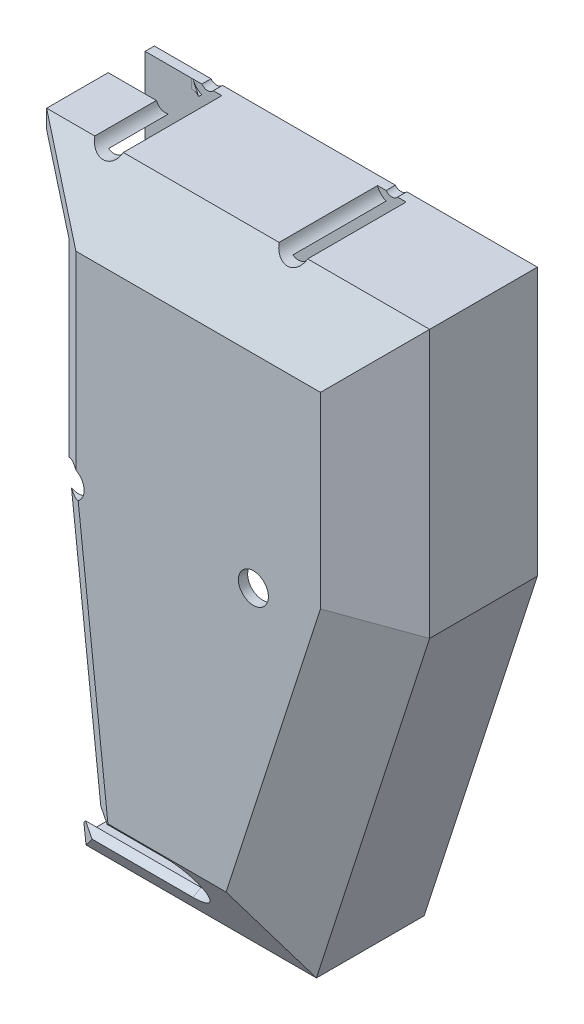
SolidWorks part; units mm, degrees
material "ABS"
ref_plane "Front Plane" through (0, 0, 0) normal (0, 0, 1) x (1, 0, 0)
ref_plane "Top Plane" through (0, 0, 0) normal (0, 1, 0) x (1, 0, 0)
ref_plane "Right Plane" through (0, 0, 0) normal (1, 0, 0) x (0, 0, -1)
sketch "Sketch1" plane through (0, 0, 0) normal (0, 0, 1) x (1, 0, 0)
  line L0 (-33.5, -29) -> (-33.5, -5) construction
  line L1 (-24.9678, -105) -> (-33.5, -29) construction
  line L2 (-24.9678, -105) -> (24.9678, -105) construction
  line L3 (49.5, -29) -> (24.9678, -105) construction
  line L4 (49.5, 29) -> (49.5, -29) construction
  line L5 (-33.5, -29) -> (-33.5, 29)
  line L6 (-24.9678, -105) -> (-33.5, -29)
  line L7 (-24.9678, -105) -> (24.9678, -105)
  line L8 (49.5, -29) -> (24.9678, -105)
  line L9 (49.5, 29) -> (49.5, -29)
  line L10 (49.5, 29) -> (-33.5, 29)
extrude "Extrude1" add sketch "Sketch1" along normal blind 32
chamfer "Chamfer1" distance 15 angle 30 6 edges at (-33.5, 0, 32) (-29.2339, -67, 32) (37.2339, -67, 32) (49.5, 0, 32) (8, 29, 32) (0, -105, 32) first distance on face at (5.3333, -35, 32)
sketch "Sketch2" plane through (-33.5, 0, 0) normal (-1, 0, 0) x (0, 0, 1)
  line L0 (2, 27) -> (22.185, 27)
  line L1 (22.185, 27) -> (30, 13.4641)
  line L2 (30, 13.4641) -> (30, -89.4641)
  line L3 (30, -89.4641) -> (22.185, -103)
  line L4 (22.185, -103) -> (2, -103)
  line L5 (2, -103) -> (2, 27)
  line L6 (0, 29) -> (0, -29) construction
  line L7 (23.3397, 29) -> (0, 29) construction
  line L8 (32, 14) -> (23.3397, 29) construction
  line L9 (32, -90) -> (23.3397, -105) construction
  line L10 (32, 14) -> (32, -28.1606) construction
  line L11 (23.3397, -105) -> (0, -105) construction
  dimension "D1" = 2
  dimension "D2" = 2
  dimension "D3" = 2
  dimension "D4" = 2
  dimension "D5" = 2
  dimension "D6" = 2
extrude "Cut-Extrude2" cut sketch "Sketch2" against normal blind 20
shell "Shell1" thickness 2 removed face at (-13.5, -38, 18.0617)
sketch "Sketch3" plane through (0, 0, 2) normal (0, 0, 1) x (1, 0, 0)
  line L0 (39.5, 0) -> (0, 0) construction
  line L1 (39.5, -5) -> (0, -5)
  line L2 (39.5, 5) -> (0, 5)
  circle A0 centre (19.9678, 30) radius 1.6 construction
  circle A1 centre (-19.9678, 30) radius 1.6 construction
  circle A2 centre (19.9678, -30) radius 1.6 construction
  circle A3 centre (-19.9678, -30) radius 1.6 construction
  circle A4 centre (19.9678, 30) radius 1.6
  circle A5 centre (-19.9678, 30) radius 1.6
  circle A6 centre (19.9678, -30) radius 1.6
  circle A7 centre (-19.9678, -30) radius 1.6
  circle A8 centre (0, -54.5) radius 20
  arc A9 (39.5, -5) -> (39.5, 5) centre (39.5, 0) ccw
  arc A10 (0, 5) -> (0, -5) centre (0, 0) ccw
  point P19 (19.75, 0)
  dimension "D1" = 40
  dimension "D2" = 5
extrude "Cut-Extrude3" cut sketch "Sketch3" against normal blind 20
sketch "Sketch4" plane through (0, 0, 2) normal (0, 0, 1) x (1, 0, 0)
  circle A0 centre (-19.9678, -30) radius 3.25
  circle A1 centre (-19.9678, 30) radius 3.25
  circle A2 centre (19.9678, 30) radius 3.25
  circle A3 centre (19.9678, -30) radius 3.25
  dimension "D1" = 6.5
extrude "Cut-Extrude5" cut sketch "Sketch4" along normal blind 39
sketch "Sketch6" plane through (0, 29, 0) normal (0, 1, 0) x (1, 0, 0)
  line L0 (-43.2864, -6) -> (-23.5, -6) construction
  line L1 (-43.2864, -2) -> (-23.5, -2)
  line L2 (-43.2864, -10) -> (-23.5, -10)
  line L3 (-21.2178, -2) -> (-33.5, -2) construction
  line L4 (-33.5, -23.3397) -> (-33.5, 0) construction
  arc A0 (-43.2864, -2) -> (-43.2864, -10) centre (-43.2864, -6) ccw
  arc A1 (-23.5, -10) -> (-23.5, -2) centre (-23.5, -6) ccw
  point P2 (-33.3932, -6)
  dimension "D1" = 4
  dimension "D2" = 10
extrude "Cut-Extrude6" cut sketch "Sketch6" against normal blind 9
sketch "Sketch7" plane through (0, 0, 2) normal (0, 0, 1) x (1, 0, 0)
  line L0 (20.0322, -100) -> (-19.9678, -100) construction
  line L1 (20.0322, -104) -> (-19.9678, -104)
  line L2 (20.0322, -96) -> (-19.9678, -96)
  arc A0 (20.0322, -104) -> (20.0322, -96) centre (20.0322, -100) ccw
  arc A1 (-19.9678, -96) -> (-19.9678, -104) centre (-19.9678, -100) ccw
  point P4 (0.0322, -100)
  dimension "D1" = 4
extrude "Cut-Extrude7" cut sketch "Sketch7" along normal blind 9 and the other way blind 9
sketch "Sketch8" plane through (0, -35.3564, 61.2391) normal (0, 0.5, -0.866) x (-1, 0, 0)
  line L0 (24.3945, -68.4782) -> (-0.6055, -68.4782) construction
  line L1 (24.3945, -74.4782) -> (-0.6055, -74.4782)
  line L2 (24.3945, -62.4782) -> (-0.6055, -62.4782)
  line L3 (-13.6574, -62.4782) -> (15.1036, -62.4782) construction
  line L5 (25.4168, -75.7987) -> (15.1036, -62.4782) construction
  arc A0 (24.3945, -74.4782) -> (24.3945, -62.4782) centre (24.3945, -68.4782) ccw
  arc A1 (-0.6055, -62.4782) -> (-0.6055, -74.4782) centre (-0.6055, -68.4782) ccw
  point P2 (11.8945, -68.4782)
  dimension "D1" = 6
  dimension "D2" = 25
extrude "Cut-Extrude8" cut sketch "Sketch8" against normal blind 9
ref_plane "Plane1" through (-15.5, 0, 0) normal (-1, 0, 0) x (0, 0, 1)
sketch "Sketch9" plane through (-15.5, 0, 0) normal (-1, 0, 0) x (0, 0, 1)
  line L0 (2, -103) -> (2, -29) construction
  line L1 (2, -75.6241) -> (6, -75.6241)
  line L2 (2, -75.6241) -> (2, -83.6241)
  line L3 (2, -83.6241) -> (6, -83.6241)
  line L5 (30, -26.5547) -> (30, 13.4641) construction
  line L6 (30, 14.7261) -> (26, 14.7261)
  line L7 (30, 14.7261) -> (30, 6.7261)
  line L8 (30, 6.7261) -> (26, 6.7261)
  line L10 (30, -89.4641) -> (30, -32.8898) construction
  line L11 (30, -47.1918) -> (26, -47.1918)
  line L12 (30, -47.1918) -> (30, -55.1918)
  line L13 (30, -55.1918) -> (26, -55.1918)
  arc A0 (6, -75.6241) -> (6, -83.6241) centre (6, -79.6241) cw
  arc A1 (26, 14.7261) -> (26, 6.7261) centre (26, 10.7261) ccw
  arc A2 (26, -47.1918) -> (26, -55.1918) centre (26, -51.1918) ccw
  circle A3 centre (26, 10.7261) radius 1.3
  circle A4 centre (6, -79.6241) radius 1.3
  circle A5 centre (26, -51.1918) radius 1.3
  circle A6 centre (26, 10.7261) radius 4 construction
  dimension "D1" = 2.6
  dimension "D2" = 4
  dimension "D3" = 4
extrude "Extrude2" add sketch "Sketch9" against normal blind 9
chamfer "Chamfer2" distance 4 angle 45 9 edges at (-6.5, -83.6241, 4) (-6.5, -75.6241, 4) (-6.5, -79.6241, 10) (-6.5, 14.7261, 27.6357) (-6.5, 6.7261, 28) (-6.5, 10.7261, 22) (-6.5, -47.1918, 28) (-6.5, -55.1918, 28) (-6.5, -51.1918, 22)
